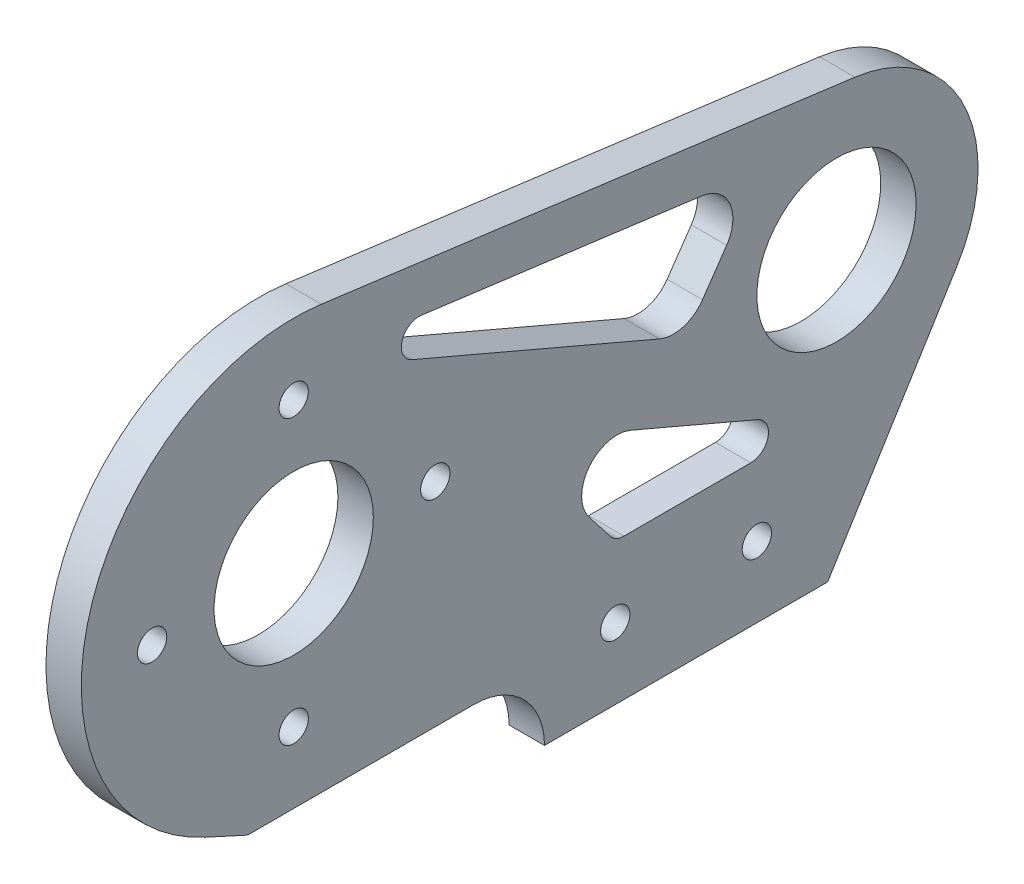
SolidWorks part; units mm, degrees
material "6061-T6 (SS)"
ref_plane "Front Plane" through (0, 0, 0) normal (0, 0, 1) x (1, 0, 0)
ref_plane "Top Plane" through (0, 0, 0) normal (0, 1, 0) x (1, 0, 0)
ref_plane "Right Plane" through (0, 0, 0) normal (1, 0, 0) x (0, 0, -1)
sketch "Sketch1" plane through (0, 0, 0) normal (1, 0, 0) x (0, 0, -1)
  line L0 (25.4, 12.7) -> (38.1, 12.7) construction
  line L1 (0, 0) -> (76.2, 0)
  line L5 (38.1, 12.7) -> (63.5, 12.7) construction
  line L6 (63.5, 12.7) -> (77.7875, 12.7) construction
  line L7 (77.7875, 12.7) -> (77.7875, 50.8) construction
  line L8 (77.7875, 50.8) -> (17.2031, 50.8) construction
  line L9 (76.2, 0) -> (99.3809, 37.4252)
  line L12 (-19.5961, 50.8) -> (-19.5961, 76.2) construction
  line L13 (0, 0) -> (-35.3956, 16.1303)
  line L15 (38.1, 12.7) -> (38.1, 39.0177) construction
  line L18 (-19.5961, 50.8) -> (-19.5961, 25.4) construction
  line L19 (-19.5961, 50.8) -> (5.8039, 50.8) construction
  line L20 (-19.5961, 50.8) -> (-44.9961, 50.8) construction
  line L21 (81.1, 75.9831) -> (-14.6274, 88.5746)
  line L22 (77.7875, 50.8) -> (-19.5961, 50.8) construction
  circle A0 centre (38.1, 12.7) radius 2.6289
  circle A1 centre (63.5, 12.7) radius 2.6289
  circle A2 centre (77.7875, 50.8) radius 14.2875
  arc A3 (99.3809, 37.4252) -> (81.1, 75.9831) centre (77.7875, 50.8) ccw
  circle A4 centre (-19.5961, 50.8) radius 14.2875
  circle A5 centre (-19.5961, 76.2) radius 2.6289
  arc A9 (-14.6274, 88.5746) -> (-35.3956, 16.1303) centre (-19.5961, 50.8) ccw
  circle A10 centre (-19.5961, 25.4) radius 2.6289
  circle A11 centre (5.8039, 50.8) radius 2.6289
  circle A12 centre (-44.9961, 50.8) radius 2.6289
  point P2 (-16.9206, 73.4701)
  point P26 (-19.5947, 51.3245)
  point P27 (-18.5651, 64.9332)
  dimension "D5" = 5.2578
  dimension "D6" = 5.2578
  dimension "D9" = 28.575
  dimension "D10" = 50.8
  dimension "D11" = 28.575
  dimension "D13" = 5.2578
  dimension "D15" = 76.2
  dimension "D17" = 5.2578
  dimension "D19" = 5.2578
  dimension "D21" = 5.2578
  dimension "D2" = 76.2
  dimension "D3" = 12.7
  dimension "D4" = 25.4
  dimension "D7" = 14.2875
  dimension "D8" = 38.1
  dimension "D12" = 25.4
  dimension "D16" = 97.3836
  dimension "D14" = 25.4
  dimension "D18" = 25.4
  dimension "D20" = 25.4
  dimension "D22" = 12.7
  dimension "D23" = 12.7
extrude "Boss-Extrude1" add sketch "Sketch1" along normal blind 6.35
sketch "Sketch2" plane through (0, 0, 0) normal (-1, 0, 0) x (0, 0, 1)
  line L1 (0, 0) -> (-25.4, 0)
  line L3 (0, 12.7) -> (-25.4, 12.7)
  line L4 (-25.4, 0) -> (-25.4, 12.7)
  line L5 (0, 12.7) -> (50.8, 12.7)
  line L7 (0, 0) -> (50.8, 0)
  line L8 (50.8, 12.7) -> (50.8, 0)
  dimension "D1" = 25.4
  dimension "D2" = 12.7
  dimension "D3" = 50.8
extrude "Cut-Extrude1" cut sketch "Sketch2" against normal blind 6.35
sketch "Sketch3" plane through (0, 0, 0) normal (-1, 0, 0) x (0, 0, 1)
  line L0 (-77.9111, 25.4) -> (-18.5039, 50.8)
  line L1 (-18.5039, 50.8) -> (-38.1, 25.4)
  line L2 (-38.1, 25.4) -> (-77.9111, 25.4)
  line L3 (-63.9602, 69.9115) -> (-50.8086, 50.8)
  line L4 (-50.8086, 50.8) -> (19.5961, 80.9021)
  line L5 (19.5961, 80.9021) -> (-63.9602, 69.9115)
  line L6 (-25.4, 0) -> (-76.2, 0) construction
  line L7 (-50.8086, 50.8) -> (-18.5039, 50.8) construction
  line L9 (-5.8039, 50.8) -> (-18.5039, 50.8) construction
  line L10 (19.5961, 76.2) -> (19.5961, 80.9021) construction
  line L11 (-81.1, 75.9831) -> (14.6274, 88.5746) construction
  circle A0 centre (-77.7875, 50.8) radius 14.2875 construction
  dimension "D4" = 22.225
  dimension "D1" = 25.4
  dimension "D2" = 12.7
  dimension "D3" = 12.7
  dimension "D5" = 12.7
  dimension "D6" = 8.255
extrude "Cut-Extrude2" cut sketch "Sketch3" against normal through all
fillet "Fillet1" radius 6.35 1 edges at (3.175, 50.8, -50.8086)
fillet "Fillet2" radius 6.35 1 edges at (3.175, 69.9115, -63.9602)
fillet "Fillet3" radius 3.175 1 edges at (3.175, 80.9021, 19.5961)
fillet "Fillet4" radius 6.35 1 edges at (3.175, 50.8, -18.5039)
fillet "Fillet5" radius 3.175 1 edges at (3.175, 25.4, -38.1)
fillet "Fillet6" radius 3.175 1 edges at (3.175, 25.4, -77.9111)
fillet "Fillet7" radius 12.7 1 edges at (3.175, 12.7, -25.4)
